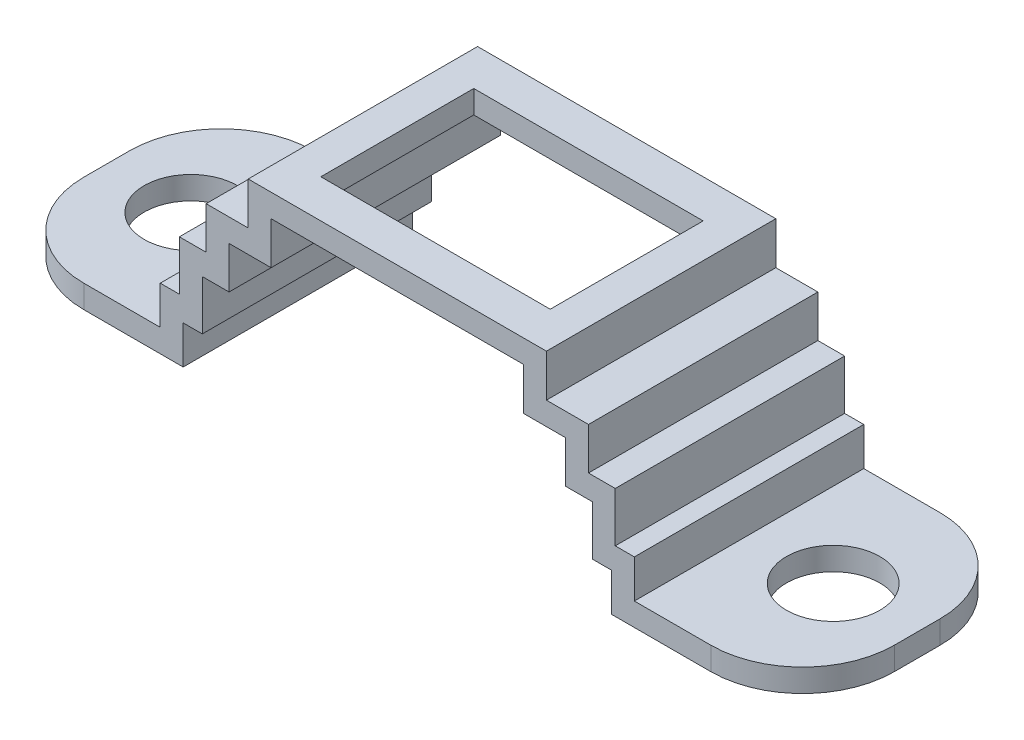
SolidWorks part; units mm, degrees
ref_plane "Front Plane" through (0, 0, 0) normal (0, 0, 1) x (1, 0, 0)
ref_plane "Top Plane" through (0, 0, 0) normal (0, 1, 0) x (1, 0, 0)
ref_plane "Right Plane" through (0, 0, 0) normal (1, 0, 0) x (0, 0, -1)
sketch "Sketch1" plane through (0, 0, 0) normal (0, 0, 1) x (1, 0, 0)
  line L0 (-53, 4.5) -> (-28, 4.5)
  line L1 (-28, 4.5) -> (-28, 9.5)
  line L2 (-28, 9.5) -> (-25.5, 9.5)
  line L3 (-25.5, 9.5) -> (-25.5, 16)
  line L4 (-25.5, 16) -> (-22, 16)
  line L5 (-22, 16) -> (-22, 21.5)
  line L6 (-22, 21.5) -> (-16.5, 21.5)
  line L7 (-16.5, 21.5) -> (-16.5, 27.05)
  line L8 (-16.5, 27.05) -> (0, 27.05)
  circle A0 centre (0, 0) radius 27.05
  dimension "D1" = 54.1
  dimension "D2" = 25
  dimension "D3" = 4.5
  dimension "D4" = 28
  dimension "D5" = 5
  dimension "D6" = 2.5
  dimension "D7" = 6.5
  dimension "D8" = 3.5
  dimension "D9" = 5.5
  dimension "D10" = 5.5
  dimension "D11" = 16.5
  dimension "D12" = 5.55
extrude "Extrude-Thin1" add sketch "Sketch1" along normal mid plane 30 thin contours L0 L1 L2 L3 L4 L5 L6 L7 L8 thin type one direction reverse wall 3
sketch "Sketch2" plane through (0, 7.5, 0) normal (0, 1, 0) x (1, 0, 0)
  line L0 (0, -15) -> (0, 15) construction
  circle A0 centre (-42, 0) radius 6.1
  dimension "D1" = 12.2
  dimension "D2" = 42
extrude "Cut-Extrude1" cut sketch "Sketch2" against normal through all
fillet "Fillet1" radius 12 2 edges at (-53, 6, -15) (-53, 6, 15)
mirror "Mirror1" about plane through (0, 30.05, 15) normal (1, 0, 0) of "Fillet1", "Cut-Extrude1", "Extrude-Thin1"
sketch "Sketch3" plane through (0, 30.05, 0) normal (0, 1, 0) x (1, 0, 0)
  line L1 (15, -10) -> (-15, -10)
  line L2 (15, -10) -> (15, 10)
  line L3 (15, 10) -> (-15, 10)
  line L4 (-15, -10) -> (-15, 10)
  line L5 (15, -10) -> (-15, 10) construction
  line L6 (15, 10) -> (-15, -10) construction
  point P0 (0, 0)
  dimension "D1" = 30
  dimension "D2" = 20
extrude "Cut-Extrude2" cut sketch "Sketch3" against normal through all
